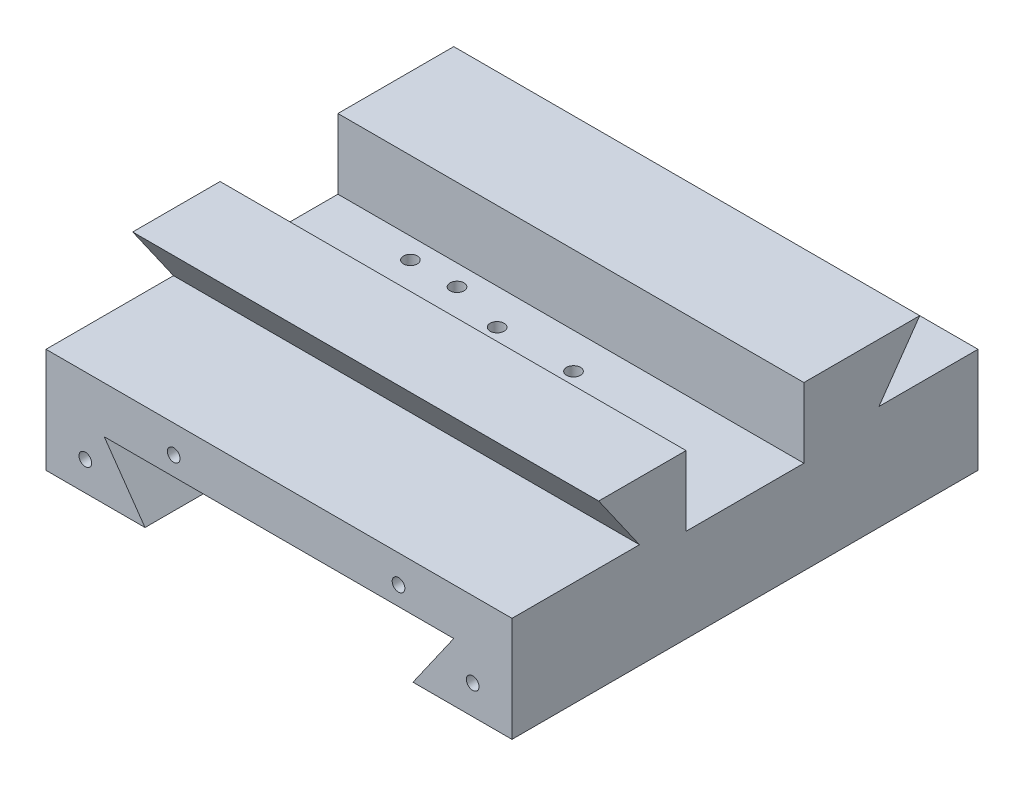
SolidWorks part; units mm, degrees
material "Ductile Iron"
ref_plane "Front Plane" through (0, 0, 0) normal (0, 0, 1) x (1, 0, 0)
ref_plane "Top Plane" through (0, 0, 0) normal (0, 1, 0) x (1, 0, 0)
ref_plane "Right Plane" through (0, 0, 0) normal (1, 0, 0) x (0, 0, -1)
sketch "female-dovetail-profile" plane through (0, 0, 0) normal (0, 0, 1) x (1, 0, 0)
  line L0 (0, 0) -> (26.9908, 0)
  line L1 (26.9908, 0) -> (15.875, 15.875)
  line L2 (15.875, 15.875) -> (111.125, 15.875)
  line L3 (111.125, 15.875) -> (100.0092, 0)
  line L4 (100.0092, 0) -> (127, 0)
  line L5 (127, 0) -> (127, 44.45)
  line L6 (127, 44.45) -> (0, 44.45)
  line L7 (0, 44.45) -> (0, 0)
  dimension "D1" = 127
  dimension "D2" = 95.25
  dimension "D3" = 55
  dimension "D4" = 55
  dimension "D5" = 15.875
  dimension "D6" = 44.45
extrude "x-carriage-extrude" add sketch "female-dovetail-profile" along normal blind 127
sketch "male-dovetail-shoulder-profile" plane through (127, 0, 0) normal (1, 0, 0) x (0, 0, -1)
  line L0 (-127, 28.575) -> (-100.0092, 28.575) construction
  line L1 (-100.0092, 28.575) -> (-111.125, 44.45) construction
  line L2 (-111.125, 44.45) -> (-127, 44.45) construction
  line L3 (-127, 44.45) -> (-127, 28.575)
  line L4 (0, 0) -> (0, 44.45)
  line L5 (0, 44.45) -> (-127, 44.45)
  line L6 (-127, 44.45) -> (-127, 0)
  line L7 (-127, 0) -> (0, 0)
  line L8 (0, 0) -> (0, 44.45) construction
  line L9 (0, 44.45) -> (-127, 44.45) construction
  line L10 (-127, 44.45) -> (-127, 0) construction
  line L11 (-127, 0) -> (0, 0) construction
  line L12 (-15.875, 44.45) -> (0, 44.45) construction
  line L13 (0, 44.45) -> (0, 28.575)
  line L14 (0, 28.575) -> (-26.9908, 28.575)
  line L15 (-26.9908, 28.575) -> (-15.875, 44.45)
  line L16 (-15.875, 44.45) -> (0, 44.45)
  line L17 (-127, 28.575) -> (-92.2573, 28.575)
  line L18 (-92.2573, 28.575) -> (-103.3731, 44.45)
  line L19 (-103.3731, 44.45) -> (-127, 44.45)
  dimension "D2" = 55
  dimension "D3" = 55
  dimension "D4" = 95.25
  dimension "D5" = 15.875
  dimension "D6" = 6.35
  dimension "D1" = 0
extrude "y-guide-cut-extrude" cut sketch "male-dovetail-shoulder-profile" against normal through all
sketch "Sketch1" plane through (0, 0, 0) normal (1, 0, 0) x (0, 0, -1)
  line L0 (-63.5, 0) -> (-63.5, 44.45) construction
  line L1 (-127, 0) -> (0, 0) construction
  line L2 (-103.3731, 44.45) -> (-15.875, 44.45) construction
  line L4 (-79.5563, 44.45) -> (-47.4437, 44.45)
  line L5 (-79.5563, 44.45) -> (-79.5563, 25.4)
  line L6 (-79.5563, 25.4) -> (-47.4437, 25.4)
  line L7 (-47.4437, 44.45) -> (-47.4437, 25.4)
  circle A0 centre (-63.5, 34.925) radius 18.669 construction
  point P10 (-63.5, 44.45)
  dimension "D2" = 37.338
  dimension "D1" = 19.05
extrude "Cut-Extrude1" cut sketch "Sketch1" along normal through all
hole_wizard "#10-24 Tapped Hole1" positions "Sketch3" profile "Sketch2" tap size "#10-24" standard "ANSI Inch" end condition up to next
sketch "Sketch3" plane through (0, 25.4, 0) normal (0, 1, 0) x (1, 0, 0)
  line L8 (0, -47.4437) -> (0, -79.5563)
  line L9 (0, -79.5563) -> (127, -79.5563)
  line L10 (127, -79.5563) -> (127, -47.4437)
  line L11 (127, -47.4437) -> (0, -47.4437)
  line L12 (0, -47.4437) -> (0, -79.5563)
  line L13 (0, -79.5563) -> (127, -79.5563)
  line L14 (127, -79.5563) -> (127, -47.4437)
  line L15 (127, -47.4437) -> (0, -47.4437)
  line L16 (0, -63.5) -> (127, -63.5) construction
  line L18 (31.75, -50.6187) -> (31.75, -82.7313) construction
  line L21 (38.1, -53.086) -> (25.4, -53.086) construction
  line L22 (38.1, -53.086) -> (38.1, -73.914) construction
  line L23 (38.1, -73.914) -> (25.4, -73.914) construction
  line L24 (25.4, -53.086) -> (25.4, -73.914) construction
  line L37 (53.086, -57.15) -> (73.914, -57.15) construction
  line L38 (73.914, -57.15) -> (73.914, -69.85) construction
  line L39 (73.914, -69.85) -> (53.086, -69.85) construction
  line L40 (53.086, -69.85) -> (53.086, -57.15) construction
  line L41 (53.086, -57.15) -> (73.914, -57.15) construction
  line L42 (73.914, -57.15) -> (73.914, -69.85) construction
  line L44 (63.5, -47.4437) -> (63.5, -79.5563) construction
  point P0 (25.4, -53.086)
  point P2 (25.4, -73.914)
  point P4 (38.1, -73.914)
  point P6 (38.1, -53.086)
  point P118 (38.1, -63.5)
  point P119 (31.75, -73.914)
  point P154 (53.086, -57.15)
  point P156 (73.914, -57.15)
  point P158 (73.914, -69.85)
  point P160 (53.086, -69.85)
  point P198 (63.5, -57.15)
  point P199 (73.914, -63.5)
  dimension "D2" = 20.828
  dimension "D3" = 12.7
  dimension "D4" = 31.75
  dimension "D5" = 20.828
  dimension "D6" = 12.7
  dimension "D1" = 0
sketch "Sketch2" plane through (25.4, 25.4, 53.086) normal (1, 0, 0) x (0, 0, 1)
  line L0 (0, 0) -> (0, 9.525)
  line L1 (0, 9.525) -> (1.8986, 9.525)
  line L2 (1.8986, 9.525) -> (1.8986, 0)
  line L5 (1.8986, 0) -> (0, 0)
  line L11 (0, -6.35) -> (0, 107.95) construction
  dimension "Thru Tap Drill Dia." = 3.7973
  dimension "Thru Tap Drill Depth" = 9.525
cosmetic thread "Hole Thread1" parameters "D2"=4.826
cosmetic thread "Hole Thread2" parameters "D2"=4.826
cosmetic thread "Hole Thread3" parameters "D2"=4.826
cosmetic thread "Hole Thread4" parameters "D2"=4.826
cosmetic thread "Hole Thread5" parameters "D2"=4.826
cosmetic thread "Hole Thread6" parameters "D2"=4.826
cosmetic thread "Hole Thread7" parameters "D2"=4.826
cosmetic thread "Hole Thread8" parameters "D2"=4.826
hole_wizard "#8-32 Tapped Hole1" positions "Sketch4" profile "Sketch5" tap size "#8-32" standard "ANSI Inch"
sketch "Sketch4" plane through (0, -15.875, 127) normal (0, 0, 1) x (1, 0, 0)
  line L0 (34.8034, 41.275) -> (34.8034, 32.512) construction
  line L3 (96.0726, 41.275) -> (96.0726, 32.512) construction
  line L6 (111.125, 31.75) -> (127, 31.75) construction
  line L7 (15.875, 31.75) -> (0, 31.75) construction
  line L8 (7.9375, 31.75) -> (13.4954, 15.875) construction
  line L9 (119.0625, 31.75) -> (113.5046, 15.875) construction
  line L22 (127, 44.45) -> (0, 44.45) construction
  line L23 (0, 44.45) -> (0, 15.875) construction
  line L24 (0, 15.875) -> (26.9908, 15.875) construction
  line L25 (26.9908, 15.875) -> (15.875, 31.75) construction
  line L26 (15.875, 31.75) -> (111.125, 31.75) construction
  line L27 (111.125, 31.75) -> (100.0092, 15.875) construction
  line L28 (100.0092, 15.875) -> (127, 15.875) construction
  line L29 (127, 15.875) -> (127, 44.45) construction
  point P0 (10.7164, 23.8125)
  point P1 (34.8034, 36.8935)
  point P2 (96.0726, 36.8935)
  point P3 (116.2836, 23.8125)
cosmetic thread "Hole Thread9" parameters "D1"=8.382, "D2"=4.1656
cosmetic thread "Hole Thread10" parameters "D1"=8.382, "D2"=4.1656
cosmetic thread "Hole Thread11" parameters "D1"=8.382, "D2"=4.1656
cosmetic thread "Hole Thread12" parameters "D1"=8.382, "D2"=4.1656
sketch "Sketch5" plane through (10.7164, 7.9375, 127) normal (1, 0, 0) x (0, -1, 0)
  line L0 (0, 0) -> (0, 13.3822)
  line L1 (0, 13.3822) -> (1.7272, 12.3444)
  line L2 (1.7272, 12.3444) -> (1.7272, 0)
  line L3 (1.7272, 0) -> (0, 0)
  line L4 (0, 13.3822) -> (-1.7272, 12.3444) construction
  line L5 (0, -6.35) -> (0, 107.95) construction
  dimension "Tap Drill Dia." = 3.4544
  dimension "Tap Drill Depth" = 12.3444
  dimension "Drill Angle" = 118
hole_wizard "#8-32 Tapped Hole2" positions "Sketch6" profile "Sketch7" tap size "#8-32" standard "ANSI Inch"
sketch "Sketch6" plane through (0, -15.875, 0) normal (0, 0, -1) x (-1, 0, 0)
  point P0 (-10.7164, 23.8125)
  point P1 (-34.8034, 36.8935)
  point P2 (-96.0726, 36.8935)
  point P3 (-116.2836, 23.8125)
cosmetic thread "Hole Thread13" parameters "D1"=8.382, "D2"=4.1656
cosmetic thread "Hole Thread14" parameters "D1"=8.382, "D2"=4.1656
cosmetic thread "Hole Thread15" parameters "D1"=8.382, "D2"=4.1656
cosmetic thread "Hole Thread16" parameters "D1"=8.382, "D2"=4.1656
sketch "Sketch7" plane through (10.7164, 7.9375, 0) normal (1, 0, 0) x (0, 1, 0)
  line L0 (0, 0) -> (0, 13.4838)
  line L1 (0, 13.4838) -> (1.7272, 12.446)
  line L2 (1.7272, 12.446) -> (1.7272, 0)
  line L5 (1.7272, 0) -> (0, 0)
  line L10 (0, 13.4838) -> (-1.7272, 12.446) construction
  line L11 (0, -6.35) -> (0, 107.95) construction
  dimension "Tap Drill Dia." = 3.4544
  dimension "Tap Drill Depth" = 12.446
  dimension "Drill Angle" = 118
hole_wizard "gib screw 1/4-20 Tapped Hole1" positions "Sketch9" profile "Sketch8" tap size "1/4-20" standard "ANSI Inch" end condition up to next
sketch "Sketch9" plane through (0, 0, 0) normal (-1, 0, 0) x (0, 0, 1)
  line L0 (127, 15.875) -> (0, 15.875) construction
  line L1 (127, 15.875) -> (0, 15.875) construction
  line L2 (63.5, 15.875) -> (63.5, 0) construction
  line L3 (127, 0) -> (0, 0) construction
  line L4 (0, 7.9375) -> (127, 7.9375) construction
  line L5 (0, 28.575) -> (0, 0) construction
  line L6 (127, 28.575) -> (127, 0) construction
  line L7 (25.4, 7.9375) -> (63.5, 7.9375) construction
  point P0 (25.4, 7.9375)
  point P16 (63.5, 7.9375)
  point P22 (63.5, 7.9375)
  point P23 (101.6, 7.9375)
  dimension "D1" = 38.1
  dimension "D2" = 3
sketch "Sketch8" plane through (0, 7.9375, 25.4) normal (0, 1, 0) x (0, 0, 1)
  line L0 (0, 0) -> (0, 21.4329)
  line L1 (0, 21.4329) -> (2.5527, 21.4329)
  line L2 (2.5527, 21.4329) -> (2.5527, 0)
  line L5 (2.5527, 0) -> (0, 0)
  line L11 (0, -6.35) -> (0, 107.95) construction
  dimension "Thru Tap Drill Dia." = 5.1054
  dimension "Thru Tap Drill Depth" = 21.4329
cosmetic thread "Hole Thread17" parameters "D2"=6.35
cosmetic thread "Hole Thread18" parameters "D2"=6.35
cosmetic thread "Hole Thread19" parameters "D2"=6.35
equation "\"dovetail-angle\"= 55"
equation "\"dovetail-stock-width\"= 5"
equation "\"dovetail-stock-height\"= 1.25"
equation "\"dovetail-depth\"= 0.5 * \"dovetail-stock-height\""
equation "\"dovetail-throat-width\"= \"dovetail-stock-width\" - (2 * \"dovetail-depth\")"
equation "\"delta-x\"= 6"
equation "\"delta-y\"= 3"
equation "\"delta-z\"= 2.5"
equation "\"gib-thickness\"= 0.25"
equation "\"x-slide-length\"= \"dovetail-stock-width\" + \"delta-x\""
equation "\"y-slide-length\"= \"dovetail-stock-width\" + \"delta-y\""
equation "\"dog-point-diam\"= .149"
equation "\"D1@female-dovetail-profile\"=\"dovetail-stock-width\""
equation "\"D2@female-dovetail-profile\"=\"dovetail-throat-width\""
equation "\"D3@female-dovetail-profile\"=\"dovetail-angle\""
equation "\"D4@female-dovetail-profile\"=\"dovetail-angle\""
equation "\"D5@female-dovetail-profile\"=\"dovetail-depth\""
equation "\"D1@x-carriage-extrude\"=\"dovetail-stock-width\""
equation "\"dog-point-length\"= .067"
equation "\"dovetail-double-height\"= 2 * \"dovetail-depth\" + 0.5"
equation "\"D6@female-dovetail-profile\"=\"dovetail-double-height\""
equation "\"D2@male-dovetail-shoulder-profile\"=\"dovetail-angle\""
equation "\"D3@male-dovetail-shoulder-profile\"=\"dovetail-angle\""
equation "\"D4@male-dovetail-shoulder-profile\"=\"dovetail-throat-width\""
equation "\"D5@male-dovetail-shoulder-profile\"=\"dovetail-depth\""
equation "\"D6@male-dovetail-shoulder-profile\"=\"gib-thickness\""
equation "\"acme-major-diam\"= .5"
equation "\"acme-pitch-diam\"= 0.45"
equation "\"acme-minor-diam\"= 0.4"
equation "\"acme-nut-od\"= 1.47"
equation "\"acme-nut-length\"= 1"
equation "\"acme-nut-trim-height\"= .75"
equation "\"screw-bearing-od\"= 0.5"
equation "\"screw-bearing-length\"= .25"
equation "\"screw-bearing-id\"= .375"
equation "\"end-plate-thickness\"= \"screw-bearing-length\""
equation "\"screw-add-length\"= 2 * \"end-plate-thickness\" + 1 + 0.5"
equation "\"x-screw-length\"= \"x-slide-length\" + \"screw-add-length\""
equation "\"y-screw-length\"= \"y-slide-length\" + \"screw-add-length\""
equation "\"D1@Sketch1\"=\"acme-nut-trim-height\""
equation "\"D2@Sketch1\"=\"acme-nut-od\""
equation "\"acme-nut-mount-hole-space-horz\"= 0.82"
equation "\"acme-nut-mount-hole-space-vert\"= 0.5 * \"acme-nut-length\""
equation "\"D2@Sketch3\"=\"acme-nut-mount-hole-space-horz\""
equation "\"D3@Sketch3\"=\"acme-nut-mount-hole-space-vert\""
equation "\"D4@Sketch3\"=\"dovetail-stock-width\"/4"
equation "\"D5@Sketch3\"=\"acme-nut-mount-hole-space-horz\""
equation "\"D6@Sketch3\"=\"acme-nut-mount-hole-space-vert\""
